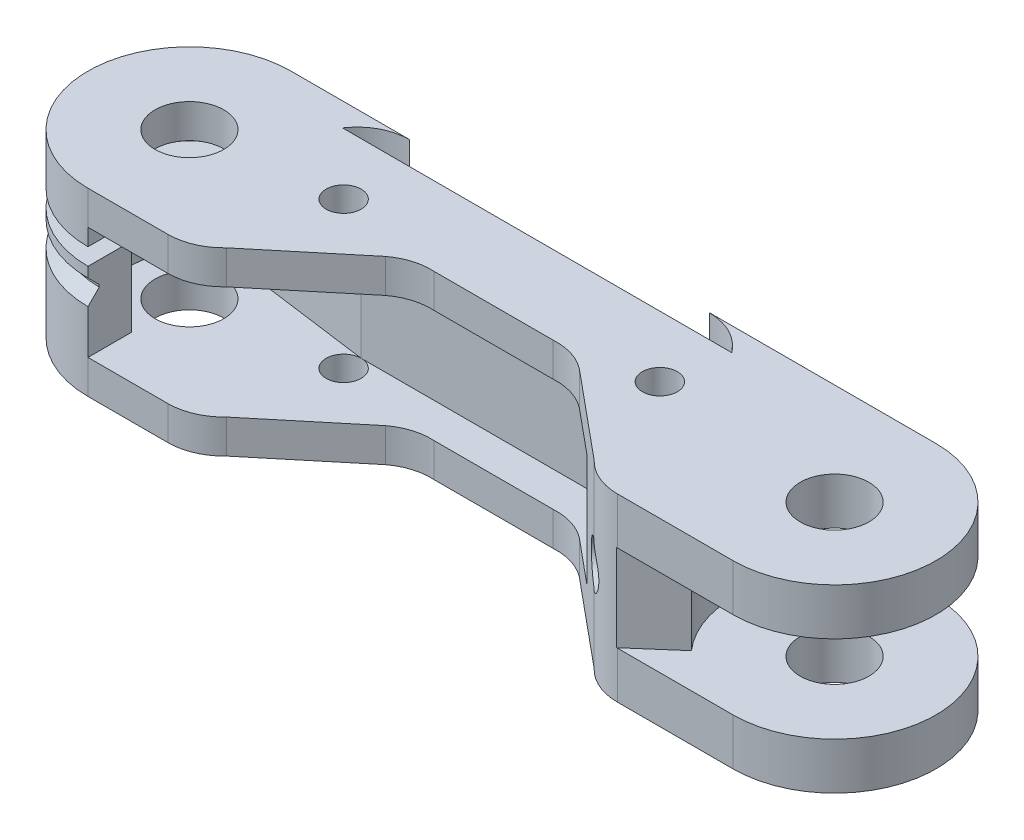
SolidWorks part; units mm, degrees
ref_plane "前视基准面" through (0, 0, 0) normal (0, 0, 1) x (1, 0, 0)
ref_plane "上视基准面" through (0, 0, 0) normal (0, 1, 0) x (1, 0, 0)
ref_plane "右视基准面" through (0, 0, 0) normal (1, 0, 0) x (0, 0, -1)
sketch "草图1" plane through (0, 0, 0) normal (0, 1, 0) x (1, 0, 0)
  line L0 (-54.8104, 0) -> (77.4698, 0) construction
  line L1 (0, 26.3055) -> (0, -33.4851) construction
  line L2 (-19.8266, 9) -> (19.8266, 9)
  line L3 (-16.3123, -7.4409) -> (-8.6054, -1.0517)
  line L4 (-5.2834, -0.0394) -> (5.2834, -0.0394)
  line L5 (-19.8266, 9) -> (-27.03, 9)
  line L6 (-27.03, 9) -> (-27.03, -13.558) construction
  line L7 (-27.03, -9) -> (-19.94, -9)
  line L8 (16.3123, -7.4409) -> (8.6054, -1.0517)
  line L9 (19.8266, 9) -> (30.2, 9)
  line L10 (19.94, -9) -> (30.2, -9)
  line L11 (30.2, 9) -> (30.2, -9) construction
  line L12 (30.2, 9) -> (30.2, -9) construction
  arc A1 (-27.03, 9) -> (-27.03, -9) centre (-27.03, 0) ccw
  arc A2 (-19.94, -9) -> (-16.3123, -7.4409) centre (-19.94, -4) ccw
  arc A3 (-5.2834, -0.0394) -> (-8.6054, -1.0517) centre (-5.5777, -5.0308) ccw
  arc A4 (19.94, -9) -> (16.3123, -7.4409) centre (19.94, -4) cw
  arc A6 (5.2834, -0.0394) -> (8.6054, -1.0517) centre (5.5777, -5.0308) cw
  arc A7 (30.2, 9) -> (30.2, -9) centre (30.2, 0) cw
  circle A8 centre (-14.85, 1.5) radius 1.55
  circle A9 centre (13.2, 1.5) radius 1.55
  circle A10 centre (-27.03, 0) radius 3.05
  circle A11 centre (30.2, 0) radius 3.05
  point P27 (0, 6.75)
  point P29 (0, -0.0394)
  dimension "D1" = 5
  dimension "D3" = 9
  dimension "D4" = 7.5
  dimension "D7" = 8.9606
  dimension "D8" = 7.09
  dimension "D12" = 9
  dimension "D6" = 7.5
  dimension "D2" = 12.18
  dimension "D5" = 14.6566
  dimension "D9" = 17
  dimension "D10" = 27.03
  dimension "D11" = 30.2
extrude "凸台-拉伸1" add sketch "草图1" along normal blind 16
ref_plane "基准面1" through (0, 8, 0) normal (0, 1, 0) x (1, 0, 0)
sketch "草图2" plane through (0, 8, 0) normal (0, 1, 0) x (1, 0, 0)
  line L1 (30.2, 9) -> (-27.03, 9) construction
  line L2 (-27.03, 9) -> (-25.3902, 9)
  line L3 (-27.03, 8) -> (-24.5321, 8)
  line L4 (-24.5321, 8) -> (-25.3902, 9)
  line L5 (-27.03, -9) -> (-27.03, -8)
  arc A0 (-27.03, 9) -> (-27.03, -9) centre (-27.03, 0) ccw construction
  arc A3 (-27.03, 9) -> (-27.03, -9) centre (-27.03, 0) ccw
  arc A6 (-27.03, 8) -> (-27.03, -8) centre (-27.03, 0) ccw
  arc A8 (-27.03, 9) -> (-27.03, -9) centre (-27.03, 0) ccw
extrude "切除-拉伸1" cut sketch "草图2" against normal mid plane 0.2 contours A6 L3 L4 L2 A3 L5 region at (-26.2101, 8, -8.7864)
chamfer "倒角1" distance 1 angle 45 4 edges at (-26.2101, 8.1, -9) (-36.03, 8.1, 0) (-26.2101, 7.9, -9) (-36.03, 7.9, 0)
sketch "草图3" plane through (0, 8, 0) normal (0, 1, 0) x (1, 0, 0)
  line L0 (-28.5589, 4.9054) -> (-14.85, 3.05)
  line L1 (-14.85, 3.05) -> (13.2, 3.05)
  line L2 (14.6565, 0.9699) -> (11.0278, -9)
  line L3 (-27.03, -5.1382) -> (-27.03, -9)
  line L4 (-27.03, -9) -> (11.0278, -9)
  circle A0 centre (-14.85, 1.5) radius 1.55 construction
  circle A1 centre (13.2, 1.5) radius 1.55 construction
  arc A3 (14.6565, 0.9699) -> (13.2, 3.05) centre (13.2, 1.5) ccw
  arc A4 (-28.5589, 4.9054) -> (-27.03, -5.1382) centre (-27.03, 0) ccw
  dimension "D1" = 70
extrude "切除-拉伸2" cut sketch "草图3" against normal mid plane 10
sketch "草图4" plane through (0, 8, 0) normal (0, 1, 0) x (1, 0, 0)
  line L0 (39.2, 0) -> (16.3123, 0) construction
  line L1 (30.2, 9) -> (-27.03, 9) construction
  line L3 (19.94, -9) -> (30.2, -9) construction
  line L4 (29.913, 9) -> (30.2, 9)
  line L5 (29.913, -9) -> (30.2, -9)
  line L6 (30.2, 9) -> (19.8748, 9)
  line L7 (30.2, 9) -> (-27.03, 9) construction
  line L8 (30.2, 9) -> (30.2, -9) construction
  line L11 (19.8748, 9) -> (23.4156, 5.9137)
  line L12 (30.2, -9) -> (19.8748, -9)
  line L13 (19.8748, -9) -> (23.4156, -5.9137)
  arc A0 (23.4156, 5.9137) -> (23.4156, -5.9137) centre (30.2, 0) ccw
  arc A1 (30.2, -9) -> (30.2, 9) centre (30.2, 0) ccw
extrude "切除-拉伸3" cut sketch "草图4" against normal mid plane 7.7 contours L5 A1 L4 L6 L11 A0 L13 L12 region at (29.6495, 8, 0)
sketch "草图5" plane through (0, 0, -9) normal (0, 0, -1) x (-1, 0, 0)
  line L0 (9.9, 8) -> (-9.9, 8) construction
  circle A0 centre (25.3902, 5.62) radius 0.75
  dimension "D1" = 2.38
extrude "切除-拉伸4" cut sketch "草图5" against normal through all
sketch "草图6" plane through (0, 0, -9) normal (0, 0, -1) x (-1, 0, 0)
  line L0 (33.0299, 11.5) -> (41.0916, 11.5)
  line L1 (41.0916, 11.5) -> (41.0916, 10)
  line L2 (41.0916, 10) -> (33.0299, 10)
  line L6 (27.0299, 10) -> (33.0299, 10)
  line L7 (27.0299, 10) -> (27.0299, 11.5)
  line L8 (27.0299, 11.5) -> (33.0299, 11.5)
  line L10 (30.0299, 11.5) -> (30.0299, 10) construction
  line L27 (27.0299, 10.75) -> (35.5266, 10.75) construction
  point P10 (30.0299, 10.75)
  dimension "D2" = 1.5
  dimension "D3" = 6
sketch "草图8" plane through (2.9885, 0, -3.6048) normal (-0.6382, 0, 0.7699) x (0.7699, 0, 0.6382)
  line L0 (17.307, 16) -> (17.307, 0) construction
  circle A0 centre (17.307, 8) radius 1.85
extrude "切除-拉伸7" cut sketch "草图8" against normal mid plane 8
sketch "草图9" plane through (0, 0, -9) normal (0, 0, -1) x (-1, 0, 0)
  line L0 (25.3902, 6.9) -> (25.3902, 9.1) construction
  circle A0 centre (25.3902, 8) radius 0.75
extrude "切除-拉伸8" cut sketch "草图9" against normal through all
sketch "草图11" plane through (0, 16, 0) normal (0, 1, 0) x (1, 0, 0)
  line L0 (-20.3758, 6.9218) -> (14.1549, 6.9218)
  line L1 (30.2, 9) -> (-27.03, 9) construction
  line L3 (0, 0) -> (0, 9.426) construction
  line L4 (-14.9251, 9) -> (10.0899, 9)
  line L5 (-14.9251, 9) -> (-16.209, 9)
  spline S0 degree 2 poles (-16.209, 9) (-18.8655, 9.0595) (-20.3758, 6.9218) knots 0 0 0 1 1 1
  spline S1 degree 2 poles (9.6927, 9) (12.4727, 9.0812) (14.1549, 6.9218) knots 0 0 0 1 1 1
  point P12 (0, 6.9218)
  point P13 (0, 6.9218)
  point P15 (0, 9)
  line M15 (30.2, 9) -> (-27.03, 9)
extrude "切除-拉伸9" cut sketch "草图11" against normal through all contours L0 L3 S0 M15 | L3 L0 S1 L4 M15 region at (-9.6297, 16, -7.9339) region at (6.4893, 16, -7.9181)
extrude "切除-拉伸10" cut sketch "草图6" against normal through all
sketch "草图12" plane through (13.0388, 0, -14.9587) normal (0.6571, 0, -0.7538) x (-0.7538, 0, -0.6571)
  line L0 (-9.0684, 11.85) -> (-13.7655, 4.15) construction
  line L1 (-13.7655, 11.85) -> (-9.0684, 4.15) construction
  circle A0 centre (-11.417, 8) radius 0.75
extrude "切除-拉伸11" cut sketch "草图12" against normal through all
